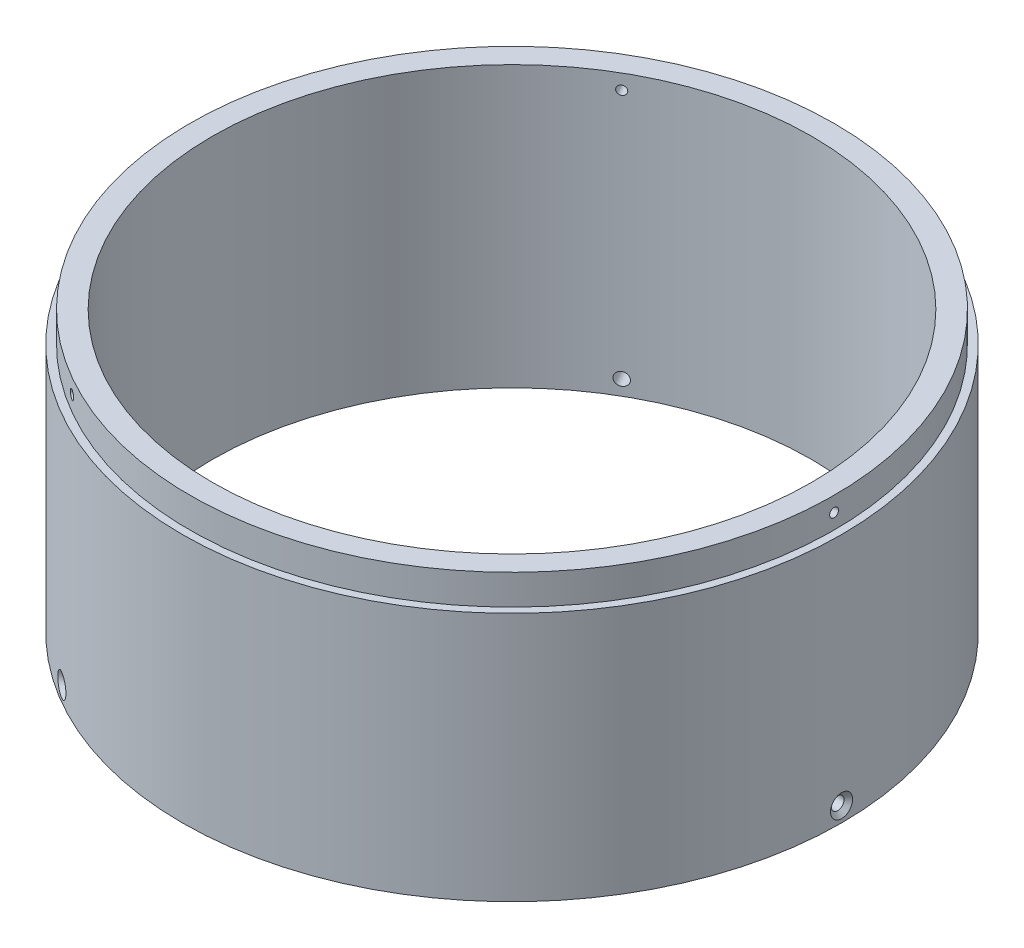
SolidWorks part; units mm, degrees
ref_plane "Front" through (0, 0, 0) normal (0, 0, 1) x (1, 0, 0)
ref_plane "Top" through (0, 0, 0) normal (0, 1, 0) x (1, 0, 0)
ref_plane "Right" through (0, 0, 0) normal (1, 0, 0) x (0, 0, -1)
sketch "Sketch1" plane through (0, 0, 0) normal (0, 0, 1) x (1, 0, 0)
  line L0 (0, 0) -> (0, 55.8674) construction
  line L1 (-76.2, 0) -> (-81.8896, 0)
  line L2 (-81.8896, 0) -> (-81.8896, -7.6708)
  line L3 (-81.8896, -7.6708) -> (-83.82, -7.6708)
  line L4 (-83.82, -7.6708) -> (-83.82, -71.1708)
  line L7 (-83.82, -71.1708) -> (-76.2, -71.1708)
  line L8 (-76.2, -71.1708) -> (-76.2, 0)
  point P5 (-83.82, -58.4708)
  dimension "D1" = 76.2
  dimension "D2" = 5.6896
  dimension "D3" = 83.82
  dimension "D4" = 50.8
  dimension "D5" = 12.7
  dimension "D6" = 7.6708
revolve "Revolve1" add sketch "Sketch1" angle 360 about L0
hole_wizard "#4-40 Tapped Hole1" positions "3DSketch1" profile "Sketch2" tap size "#4-40" standard "ANSI Inch" end condition up to next
sketch3d "3DSketch1"
  point P0 (81.8896, -3.81, 0)
  dimension "D1" = 3.81
sketch "Sketch2" plane through (81.8896, -3.81, 0) normal (0, 1, 0) x (0, 0, -1)
  line L0 (0, 0) -> (0, 163.7792)
  line L1 (0, 163.7792) -> (1.1303, 163.7792)
  line L2 (1.1303, 163.7792) -> (1.1303, 0)
  line L5 (1.1303, 0) -> (0, 0)
  line L11 (0, -6.35) -> (0, 107.95) construction
  dimension "Thread Major Dia." = 2.2606
  dimension "Thru Tap Drill Depth" = 163.7792
hole_wizard "CSK for #4 Flat Head Machine Screw (100)1" positions "3DSketch2" profile "Sketch3" countersink size "#4" standard "ANSI Inch" end condition up to next
sketch3d "3DSketch2"
  point P0 (83.82, -67.3608, 0)
  dimension "D1" = 3.81
sketch "Sketch3" plane through (83.82, -67.3608, 0) normal (0, 1, 0) x (0, 0, -1)
  line L0 (0, 0) -> (0, 167.64)
  line L1 (0, 167.64) -> (1.6319, 167.64)
  line L2 (1.6319, 167.64) -> (1.6319, 1.0284)
  line L3 (1.6319, 1.0284) -> (2.8575, 0)
  line L5 (2.8575, 0) -> (0, 0)
  line L6 (-1.6319, 1.0284) -> (-2.8575, 0) construction
  line L11 (0, -6.35) -> (0, 107.95) construction
  dimension "Thru Hole Dia." = 3.2639
  dimension "Thru Hole Depth" = 167.64
  dimension "Near C'Sink Dia." = 5.715
  dimension "Near C'Sink Angle" = 100
pattern_circular "CirPattern1" count 3 over 360 about axis through (0, 0, 0) along (0, -1, 0) of "#4-40 Tapped Hole1", "CSK for #4 Flat Head Machine Screw (100)1"
